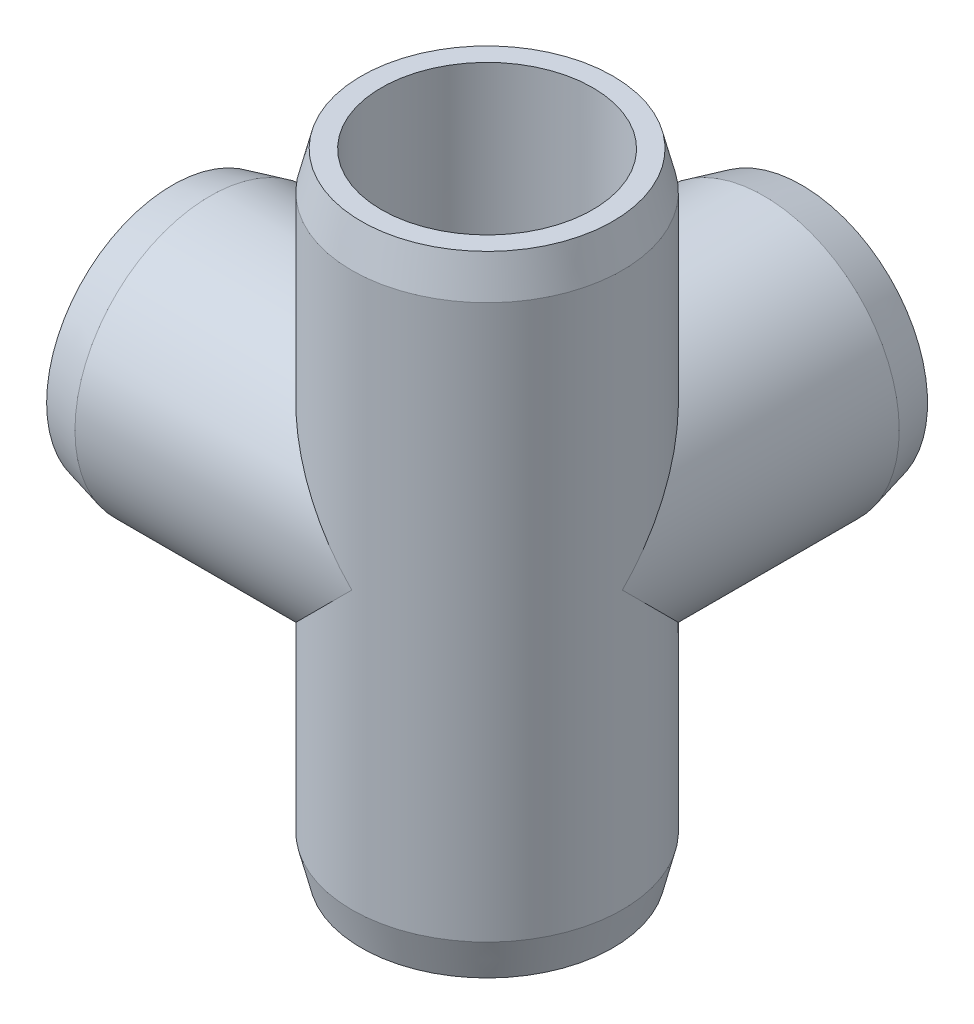
SolidWorks part; units mm, degrees
ref_plane "Front Plane" through (0, 0, 0) normal (0, 0, 1) x (1, 0, 0)
ref_plane "Top Plane" through (0, 0, 0) normal (0, 1, 0) x (1, 0, 0)
ref_plane "Right Plane" through (0, 0, 0) normal (1, 0, 0) x (0, 0, -1)
sketch "Sketch1" plane through (0, 0, 0) normal (0, 1, 0) x (1, 0, 0)
  circle A0 centre (0, 0) radius 10.668
  circle A1 centre (0, 0) radius 13.6525
  dimension "D1" = 27.305
  dimension "D2" = 21.336
extrude "Boss-Extrude1" add sketch "Sketch1" along normal blind 63.5
sketch "Sketch3" plane through (0, 0, 0) normal (0, 0, 1) x (1, 0, 0)
  line L0 (0, 0) -> (0, 63.5) construction
  circle A0 centre (0, 31.75) radius 10.668
  dimension "D2" = 21.336
  dimension "D1" = 63.5
extrude "Cut-Extrude2" cut sketch "Sketch3" against normal blind 69.85
ref_plane "Plane1" through (0, 0, -31.75) normal (0, 0, 1) x (1, 0, 0)
sketch "Sketch4" plane through (0, 0, -31.75) normal (0, 0, 1) x (1, 0, 0)
  line L0 (0, 0) -> (0, 63.5) construction
  circle A0 centre (0, 31.75) radius 13.6525
  circle A1 centre (0, 31.75) radius 10.668
  dimension "D2" = 27.305
  dimension "D3" = 21.336
  dimension "D1" = 63.5
  dimension "D4" = 31.75
extrude "Boss-Extrude2" add sketch "Sketch4" along normal up to surface (31.75 mm away) up to face at (1.6119, 21.2045, -13.557)
sketch "Sketch5" plane through (0, 0, 0) normal (1, 0, 0) x (0, 0, -1)
  line L0 (0, 0) -> (0, 63.5) construction
  circle A1 centre (0, 31.75) radius 10.668
  dimension "D2" = 21.336
  dimension "D1" = 63.5
extrude "Cut-Extrude3" cut sketch "Sketch5" against normal blind 69.85
ref_plane "Plane2" through (-31.75, 0, 0) normal (1, 0, 0) x (0, 0, -1)
sketch "Sketch6" plane through (-31.75, 0, 0) normal (1, 0, 0) x (0, 0, -1)
  line L0 (0, 0) -> (0, 63.5) construction
  circle A0 centre (0, 31.75) radius 13.6525
  circle A1 centre (0, 31.75) radius 10.668
  dimension "D2" = 27.305
  dimension "D3" = 21.336
  dimension "D1" = 63.5
extrude "Boss-Extrude3" add sketch "Sketch6" along normal up to surface (31.75 mm away) up to face at (0, 0, 13.6525)
sketch "Sketch8" plane through (0, 0, 0) normal (0, 0, 1) x (1, 0, 0)
  circle A0 centre (0, 31.75) radius 10.668
  dimension "D1" = 21.336
extrude "Cut-Extrude5" cut sketch "Sketch8" against normal blind 69.85
sketch "Sketch10" plane through (0, 0, 0) normal (0, 0, 1) x (1, 0, 0)
  line L0 (10.668, 63.5) -> (-10.668, 63.5) construction
  line L1 (10.668, 63.5) -> (-10.668, 63.5) construction
  line L2 (-10.4775, 44.45) -> (-9.2075, 44.45)
  line L3 (-9.2075, 44.45) -> (-9.2075, 42.545)
  line L4 (-9.2075, 42.545) -> (-10.4775, 42.545)
  line L5 (-10.4775, 42.545) -> (-10.4775, 44.45)
  line L6 (0, 63.5) -> (0, 11.6293) construction
  dimension "D1" = 19.05
  dimension "D2" = 1.27
  dimension "D3" = 1.905
  dimension "D4" = 3.175
sketch "Sketch11" plane through (0, 0, 0) normal (0, 0, 1) x (1, 0, 0)
  line L0 (-10.668, 0) -> (10.668, 0) construction
  line L1 (-10.668, 0) -> (10.668, 0) construction
  line L2 (-10.4775, 19.05) -> (-9.2075, 19.05)
  line L3 (-9.2075, 19.05) -> (-9.2075, 20.955)
  line L4 (-9.2075, 20.955) -> (-10.4775, 20.955)
  line L5 (-10.4775, 20.955) -> (-10.4775, 19.05)
  line L6 (0, 0) -> (0, 49.8766) construction
  dimension "D1" = 1.905
  dimension "D2" = 1.27
  dimension "D3" = 19.05
  dimension "D4" = 3.175
sketch "Sketch12" plane through (0, 0, 0) normal (0, 0, 1) x (1, 0, 0)
  line L0 (-31.75, 42.418) -> (-31.75, 21.082) construction
  line L1 (-31.75, 42.418) -> (-31.75, 21.082) construction
  line L2 (-10.795, 42.2275) -> (-10.795, 40.9575)
  line L3 (-10.795, 40.9575) -> (-12.7, 40.9575)
  line L4 (-12.7, 40.9575) -> (-12.7, 42.2275)
  line L5 (-12.7, 42.2275) -> (-10.795, 42.2275)
  line L6 (-31.75, 31.75) -> (3.4291, 31.75) construction
  dimension "D1" = 1.905
  dimension "D2" = 1.27
  dimension "D3" = 3.175
  dimension "D4" = 19.05
ref_plane "Plane3" through (0, 0, -4.445) normal (0, 0, -1) x (-1, 0, 0)
revolve "Revolve1" add sketch "Sketch10" angle 360 about L6
revolve "Revolve5" add sketch "Sketch11" angle 360 about L6
revolve "Revolve6" add sketch "Sketch12" angle 360 about L6
sketch "Sketch13" plane through (0, 0, 0) normal (1, 0, 0) x (0, 0, -1)
  line L0 (31.75, 42.418) -> (12.7, 42.418) construction
  line L1 (31.75, 42.418) -> (10.668, 42.418) construction
  line L2 (12.7, 42.418) -> (12.7, 41.148)
  line L3 (12.7, 41.148) -> (10.795, 41.148)
  line L4 (10.795, 41.148) -> (10.795, 42.418)
  line L5 (10.795, 42.418) -> (12.7, 42.418)
  line L6 (31.75, 21.082) -> (31.75, 42.418) construction
  line L7 (31.75, 21.082) -> (31.75, 42.418) construction
  line L8 (31.75, 31.75) -> (-5.1648, 31.75) construction
  dimension "D1" = 19.05
  dimension "D2" = 1.905
  dimension "D3" = 1.27
revolve "Revolve7" add sketch "Sketch13" angle 360 about L8
sketch "Sketch14" plane through (0, 0, 0) normal (1, 0, 0) x (0, 0, -1)
  line L0 (-13.6525, 0) -> (13.6525, 0) construction
  line L1 (-13.6525, 0) -> (13.6525, 0) construction
  line L2 (13.6525, 0) -> (13.6525, 3.81)
  line L3 (13.6525, 0) -> (13.6525, 18.0975) construction
  line L4 (0, 0) -> (12.7, 0) construction
  line L5 (12.7, 0) -> (13.6525, 0)
  line L6 (13.6525, 0) -> (13.7035, 0.1387)
  line L7 (12.7, 0) -> (13.6525, 3.81)
  line L8 (0, 0) -> (0, 19.4643) construction
  dimension "D1" = 3.81
  dimension "D2" = 0.9525
revolve "Cut-Revolve1" cut sketch "Sketch14" angle 360 about L8
ref_plane "Plane4" through (0, 31.75, 0) normal (0, 1, 0) x (1, 0, 0)
mirror "Mirror1" about plane through (0, 31.75, 0) normal (0, 1, 0) of "Cut-Revolve1"
sketch "Sketch15" plane through (0, 31.75, 0) normal (0, 1, 0) x (1, 0, 0)
  line L0 (13.6525, 31.75) -> (-13.6525, 31.75) construction
  line L1 (13.6525, 31.75) -> (-13.6525, 31.75) construction
  line L2 (-13.6525, 31.75) -> (-13.6525, 27.94)
  line L3 (-13.6525, 31.75) -> (-13.6525, 13.6525) construction
  line L4 (-13.6525, 31.75) -> (-12.7, 31.75)
  line L5 (-13.6525, 27.94) -> (-12.7, 31.75)
  line L6 (0, 31.75) -> (0, 28.8121) construction
  dimension "D1" = 3.81
  dimension "D2" = 0.9525
revolve "Cut-Revolve2" cut sketch "Sketch15" angle 360 about L6
sketch "Sketch16" plane through (0, 31.75, 0) normal (0, 1, 0) x (1, 0, 0)
  line L0 (-31.75, 13.6525) -> (-31.75, -13.6525) construction
  line L1 (-31.75, 13.6525) -> (-31.75, -13.6525) construction
  line L2 (-31.75, -13.6525) -> (-27.94, -13.6525)
  line L3 (-31.75, -13.6525) -> (0, -13.6525) construction
  line L4 (-31.75, -13.6525) -> (-31.75, -12.7)
  line L5 (-27.94, -13.6525) -> (-31.75, -12.7)
  line L6 (-31.75, 0) -> (-29.6083, 0) construction
  dimension "D1" = 3.81
  dimension "D2" = 0.9525
revolve "Cut-Revolve3" cut sketch "Sketch16" angle 360 about L6
